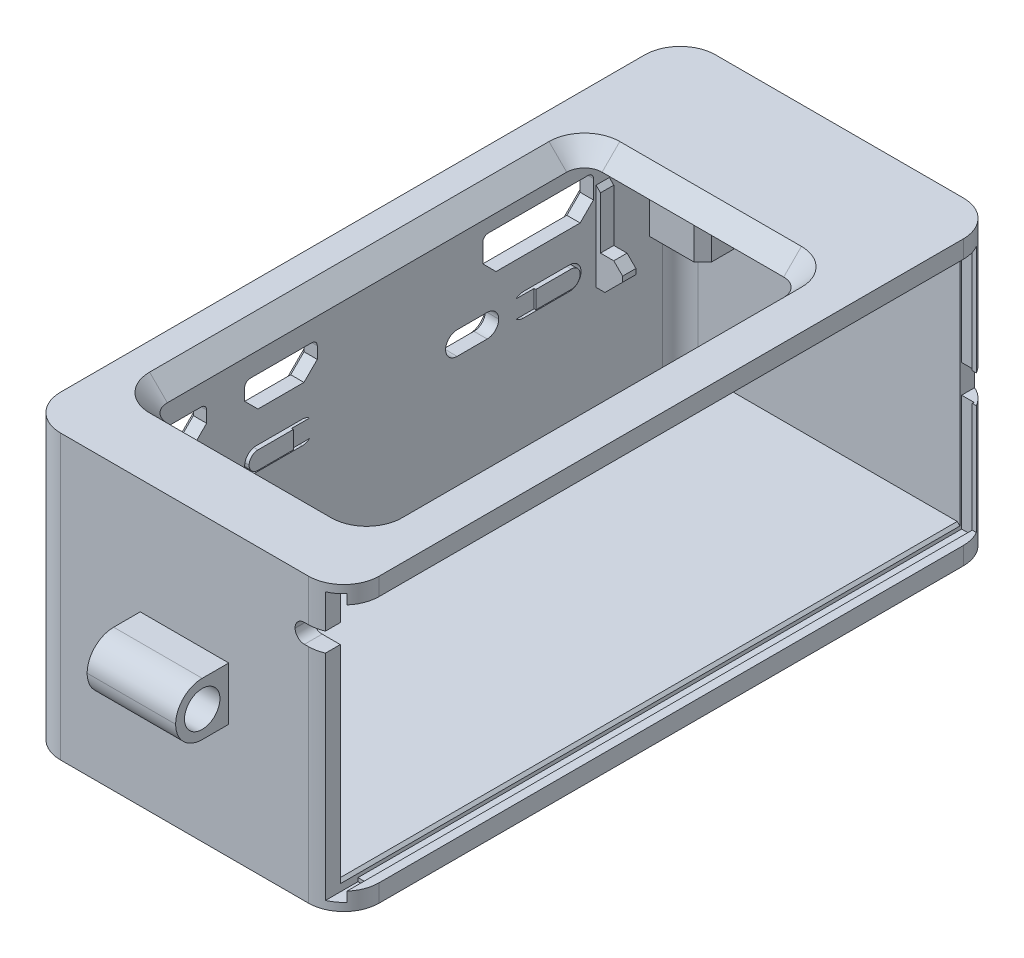
SolidWorks part; units mm, degrees
ref_plane "前视基准面" through (0, 0, 0) normal (0, 0, 1) x (1, 0, 0)
ref_plane "上视基准面" through (0, 0, 0) normal (0, 1, 0) x (1, 0, 0)
ref_plane "右视基准面" through (0, 0, 0) normal (1, 0, 0) x (0, 0, -1)
sketch "草图1" plane through (0, 0, 0) normal (1, 0, 0) x (0, 0, -1)
  line L1 (-54.0501, 29.0398) -> (19.9499, 29.0398)
  line L2 (-54.0501, 29.0398) -> (-54.0501, -2.9602)
  line L3 (-54.0501, -2.9602) -> (19.9499, -2.9602)
  line L4 (19.9499, 29.0398) -> (19.9499, -2.9602)
  dimension "D1" = 74
  dimension "D2" = 32
extrude "凸台-拉伸1" add sketch "草图1" along normal blind 36
sketch "草图2" plane through (36, 0, 0) normal (1, 0, 0) x (0, 0, -1)
  line L8 (17.9499, -0.9602) -> (17.9499, 27.0398)
  line L9 (-52.0501, -0.9602) -> (17.9499, -0.9602)
  line L10 (-52.0501, 27.0398) -> (-52.0501, -0.9602)
  line L11 (17.9499, 27.0398) -> (-52.0501, 27.0398)
  line L12 (17.9499, -0.9602) -> (17.9499, 27.0398)
  line L13 (-52.0501, -0.9602) -> (17.9499, -0.9602)
  line L14 (-52.0501, 27.0398) -> (-52.0501, -0.9602)
  line L15 (17.9499, 27.0398) -> (-52.0501, 27.0398)
  dimension "D1" = 2
extrude "切除-拉伸1" cut sketch "草图2" against normal blind 34
fillet "圆角1" radius 2 2 edges at (2, 13.0398, -17.9499) (2, 13.0398, 52.0501)
fillet "圆角2" radius 4 4 edges at (0, 13.0398, -19.9499) (0, 13.0398, 54.0501) (36, 13.0398, 54.0501) (36, 13.0398, -19.9499)
sketch "草图3" plane through (0, 29.0398, 0) normal (0, 1, 0) x (1, 0, 0)
  line L0 (32, 19.9499) -> (4, 19.9499) construction
  line L1 (29.59, 4.0599) -> (5.07, 4.0599)
  line L2 (29.59, 4.0599) -> (29.59, -45.0601)
  line L3 (29.59, -45.0601) -> (5.07, -45.0601)
  line L4 (5.07, 4.0599) -> (5.07, -45.0601)
  line L5 (36, 15.9499) -> (36, -50.0501) construction
  line L6 (32, -54.0501) -> (4, -54.0501) construction
  line L7 (0, 15.9499) -> (0, -50.0501) construction
  dimension "D1" = 15.89
  dimension "D2" = 6.41
  dimension "D3" = 8.99
  dimension "D4" = 5.07
extrude "切除-拉伸2" cut sketch "草图3" against normal blind 10
fillet "圆角3" radius 2 4 edges at (5.07, 28.0398, 45.0601) (29.59, 28.0398, 45.0601) (29.59, 28.0398, -4.0599) (5.07, 28.0398, -4.0599)
chamfer "倒角1" distance 2 angle 45 8 edges at (17.33, 29.0398, 45.0601) (29.0042, 29.0398, 44.4744) (5.6558, 29.0398, 44.4744) (29.59, 29.0398, 20.5001) (5.07, 29.0398, 20.5001) (29.0042, 29.0398, -3.4741) (5.6558, 29.0398, -3.4741) (17.33, 29.0398, -4.0599)
sketch "草图4" plane through (0, 0, 0) normal (-1, 0, 0) x (0, 0, 1)
  line L0 (-15.9499, 29.0398) -> (50.0501, 29.0398) construction
  line L1 (-8.1499, 22.4398) -> (4.3501, 22.4398)
  line L2 (-8.1499, 22.4398) -> (-8.1499, 18.2398)
  line L3 (-8.1499, 18.2398) -> (4.3501, 18.2398)
  line L4 (4.3501, 22.4398) -> (4.3501, 18.2398)
  line L5 (23.0501, 21.6812) -> (31.2501, 21.6812)
  line L6 (23.0501, 21.6812) -> (23.0501, 18.2398)
  line L7 (23.0501, 18.2398) -> (31.2501, 18.2398)
  line L8 (31.2501, 21.6812) -> (31.2501, 18.2398)
  line L9 (35.5501, 21.6398) -> (43.7501, 21.6398)
  line L10 (35.5501, 21.6398) -> (35.5501, 18.2398)
  line L11 (35.5501, 18.2398) -> (43.7501, 18.2398)
  line L12 (43.7501, 21.6398) -> (43.7501, 18.2398)
  line L13 (-6.7499, 14.7398) -> (1.0501, 14.7398)
  line L14 (-6.7499, 14.7398) -> (-6.7499, 12.1398)
  line L15 (-6.7499, 12.1398) -> (1.0501, 12.1398)
  line L16 (1.0501, 14.7398) -> (1.0501, 12.1398)
  line L17 (23.4501, 14.7398) -> (31.2501, 14.7398)
  line L18 (23.4501, 14.7398) -> (23.4501, 12.1398)
  line L19 (23.4501, 12.1398) -> (31.2501, 12.1398)
  line L20 (31.2501, 14.7398) -> (31.2501, 12.1398)
  line L21 (33.8696, 14.7398) -> (43.3696, 14.7398)
  line L22 (33.8696, 14.7398) -> (33.8696, 11.5398)
  line L23 (33.8696, 11.5398) -> (43.3696, 11.5398)
  line L24 (43.3696, 14.7398) -> (43.3696, 11.5398)
  line L25 (54.0501, 29.0398) -> (54.0501, -2.9602) construction
  line L27 (8.5501, 14.7398) -> (2.5501, 14.7398)
  line L28 (8.5501, 14.7398) -> (8.5501, 12.1398)
  line L29 (8.5501, 12.1398) -> (2.5501, 12.1398)
  line L30 (2.5501, 14.7398) -> (2.5501, 12.1398)
  dimension "D1" = 14.3
  dimension "D2" = 3.2
  dimension "D3" = 2.6
  dimension "D4" = 7.8
  dimension "D5" = 7.8
  dimension "D6" = 8.2
  dimension "D7" = 8.2
  dimension "D8" = 3.4
  dimension "D9" = 12.5
  dimension "D10" = 4.2
  dimension "D11" = 10.8
  dimension "D12" = 10.3
  dimension "D13" = 4.3
  dimension "D14" = 18.7
  dimension "D15" = 9.5
  dimension "D16" = 53
  dimension "D17" = 1.5
  dimension "D18" = 6
extrude "切除-拉伸3" cut sketch "草图4" against normal blind 10
fillet "圆角8" radius 1.3 4 edges at (1, 14.7398, 2.5501) (1, 14.7398, 8.5501) (1, 12.1398, 8.5501) (1, 12.1398, 2.5501)
sketch "草图5" plane through (2, 0, 0) normal (1, 0, 0) x (0, 0, -1)
  line L0 (-23.4501, 12.1398) -> (-23.4501, 14.7398) construction
  line L1 (-23.4501, 14.4398) -> (-30.9501, 14.4398)
  line L2 (-23.4501, 14.4398) -> (-23.4501, 12.4398)
  line L3 (-23.4501, 12.4398) -> (-30.9501, 12.4398)
  line L4 (-30.9501, 14.4398) -> (-30.9501, 12.4398)
  line L5 (-1.0501, 14.7398) -> (-1.0501, 12.1398) construction
  line L6 (-1.0501, 12.4398) -> (6.4499, 12.4398)
  line L7 (-1.0501, 12.4398) -> (-1.0501, 14.4398)
  line L8 (-1.0501, 14.4398) -> (6.4499, 14.4398)
  line L9 (6.4499, 12.4398) -> (6.4499, 14.4398)
  line L10 (-23.4501, 14.7398) -> (-31.2501, 14.7398) construction
  line L11 (-31.2501, 12.1398) -> (-23.4501, 12.1398) construction
  line L12 (-31.2501, 14.7398) -> (-31.2501, 12.1398) construction
  line L13 (6.7499, 14.7398) -> (-1.0501, 14.7398) construction
  line L14 (-1.0501, 12.1398) -> (6.7499, 12.1398) construction
  line L15 (6.7499, 12.1398) -> (6.7499, 14.7398) construction
  dimension "D1" = 0.3
  dimension "D2" = 0.3
  dimension "D3" = 0.3
  dimension "D4" = 0.3
  dimension "D5" = 0.3
  dimension "D6" = 0.3
extrude "凸台-拉伸2" add sketch "草图5" against normal blind 1.2
sketch "草图6" plane through (0.8, 0, 0) normal (-1, 0, 0) x (0, 0, 1)
  line L0 (1.0501, 12.4398) -> (-6.4499, 12.4398) construction
  line L1 (-6.4499, 14.4398) -> (-1.4499, 14.4398)
  line L2 (-6.4499, 14.4398) -> (-6.4499, 12.4398)
  line L3 (-6.4499, 12.4398) -> (-1.4499, 12.4398)
  line L4 (-1.4499, 14.4398) -> (-1.4499, 12.4398)
  line L5 (30.9501, 12.4398) -> (23.4501, 12.4398) construction
  line L6 (30.9501, 14.4398) -> (25.9501, 14.4398)
  line L7 (30.9501, 14.4398) -> (30.9501, 12.4398)
  line L8 (30.9501, 12.4398) -> (25.9501, 12.4398)
  line L9 (25.9501, 14.4398) -> (25.9501, 12.4398)
  dimension "D1" = 5
  dimension "D2" = 5
extrude "凸台-拉伸3" add sketch "草图6" along normal blind 1.5 and the other way blind 1.4
fillet "圆角4" radius 0.6 10 edges at (1, 11.5398, 33.8696) (1, 14.7398, 33.8696) (1, 14.7398, 43.3696) (1, 11.5398, 43.3696) (1, 21.6398, 35.5501) (1, 21.6398, 43.7501) (1, 21.6812, 31.2501) (1, 21.6812, 23.0501) (1, 22.4398, -8.1499) (1, 22.4398, 4.3501)
chamfer "倒角2" distance 1.5 angle 45 6 edges at (1, 18.2398, 43.7501) (1, 18.2398, 35.5501) (1, 18.2398, 31.2501) (1, 18.2398, 23.0501) (1, 18.2398, 4.3501) (1, 18.2398, -8.1499)
fillet "圆角5" radius 1 8 edges at (0.05, 12.4398, 25.9501) (0.05, 14.4398, 25.9501) (0.75, 12.4398, 30.9501) (0.75, 14.4398, 30.9501) (0.05, 12.4398, -1.4499) (0.05, 14.4398, -1.4499) (0.75, 12.4398, -6.4499) (0.75, 14.4398, -6.4499)
chamfer "倒角10" distance 0.2 angle 45 12 edges at (-0.7, 12.4398, 28.4501) (-0.7, 12.7327, 30.6572) (-0.7, 12.7327, 26.243) (-0.7, 14.1469, 30.6572) (-0.7, 14.1469, 26.243) (-0.7, 14.4398, 28.4501) (-0.7, 12.4398, -3.9499) (-0.7, 12.7327, -1.7428) (-0.7, 12.7327, -6.157) (-0.7, 14.1469, -1.7428) (-0.7, 14.1469, -6.157) (-0.7, 14.4398, -3.9499)
fillet "圆角6" radius 1.3 8 edges at (1, 14.7398, 1.0501) (1, 12.1398, 1.0501) (1, 12.1398, -6.7499) (1, 14.7398, -6.7499) (1, 14.7398, 23.4501) (1, 12.1398, 23.4501) (1, 12.1398, 31.2501) (1, 14.7398, 31.2501)
chamfer "倒角4" distance 0.5 angle 45 50 edges at (0, 12.1398, -2.8499) (0, 12.5206, 0.6694) (0, 12.5206, -6.3691) (0, 14.359, 0.6694) (0, 14.359, -6.3691) (0, 14.7398, -2.8499) (0, 18.9898, -7.3999) (0, 18.2398, -1.8999) (0, 18.9898, 3.6001) (0, 20.7898, 4.3501) (0, 20.7898, -8.1499) (0, 22.2641, 4.1744) (0, 22.2641, -7.9741) (0, 22.4398, -1.8999) (0, 11.5398, 38.6196) (0, 11.7155, 43.1938) (0, 11.7155, 34.0453) (0, 13.1398, 43.3696) (0, 13.1398, 33.8696) (0, 14.5641, 43.1938) (0, 14.5641, 34.0453) (0, 14.7398, 38.6196) (0, 12.1398, 27.3501) (0, 12.5206, 30.8694) (0, 12.5206, 23.8309) (0, 14.359, 30.8694) (0, 14.359, 23.8309) (0, 14.7398, 27.3501) (0, 20.4105, 23.0501) (0, 21.5055, 23.2259) (0, 21.6812, 27.1501) (0, 21.5055, 31.0744) (0, 18.9898, 23.8001) (0, 18.2398, 27.1501) (0, 18.9898, 30.5001) (0, 20.4105, 31.2501) (0, 18.9898, 43.0001) (0, 18.2398, 39.6501) (0, 18.9898, 36.3001) (0, 20.3898, 35.5501) (0, 21.4641, 35.7259) (0, 21.6398, 39.6501) (0, 20.3898, 43.7501) (0, 21.4641, 43.5744) (0, 12.5206, 8.1694) (0, 12.1398, 5.5501) (0, 12.5206, 2.9309) (0, 14.359, 8.1694) (0, 14.7398, 5.5501) (0, 14.359, 2.9309)
sketch "草图7" plane through (2, 0, 0) normal (1, 0, 0) x (0, 0, -1)
  line L0 (15.9499, 27.0398) -> (-50.0501, 27.0398) construction
  line L1 (-46.0501, 21.0398) -> (-44.5501, 21.0398)
  line L2 (-46.0501, 21.0398) -> (-46.0501, 11.0398)
  line L3 (-46.0501, 11.0398) -> (-44.5501, 11.0398)
  line L4 (-44.5501, 21.0398) -> (-44.5501, 11.0398)
  line L5 (8.4499, 21.0398) -> (9.9499, 21.0398)
  line L6 (8.4499, 21.0398) -> (8.4499, 11.0398)
  line L7 (8.4499, 11.0398) -> (9.9499, 11.0398)
  line L8 (9.9499, 21.0398) -> (9.9499, 11.0398)
  line L11 (17.9499, -0.9602) -> (17.9499, 27.0398) construction
  line L12 (-52.0501, 27.0398) -> (-52.0501, -0.9602) construction
  dimension "D1" = 6
  dimension "D2" = 10
  dimension "D3" = 1.5
  dimension "D4" = 1.5
  dimension "D5" = 8
  dimension "D6" = 6
extrude "凸台-拉伸4" add sketch "草图7" along normal blind 0.5
sketch "草图10" plane through (2.5, 0, 0) normal (1, 0, 0) x (0, 0, -1)
  line L1 (-46.0501, 11.0398) -> (-44.5501, 11.0398)
  line L2 (-46.0501, 11.0398) -> (-46.0501, 14.6398)
  line L3 (-46.0501, 14.6398) -> (-44.5501, 14.6398)
  line L4 (-44.5501, 11.0398) -> (-44.5501, 14.6398)
  line L7 (8.4499, 11.0398) -> (9.9499, 11.0398)
  line L8 (8.4499, 11.0398) -> (8.4499, 14.6398)
  line L9 (8.4499, 14.6398) -> (9.9499, 14.6398)
  line L10 (9.9499, 11.0398) -> (9.9499, 14.6398)
  dimension "D1" = 3.6
extrude "凸台-拉伸6" add sketch "草图10" along normal blind 2.5
chamfer "倒角7" distance 1 angle 45 2 edges at (5, 14.6398, -9.1999) (5, 14.6398, 45.3001)
chamfer "倒角8" distance 2 angle 45 2 edges at (5, 11.0398, 45.3001) (5, 11.0398, -9.1999)
chamfer "倒角5" distance 0.5 angle 45 2 edges at (2.5, 21.0398, 45.3001) (2.5, 21.0398, -9.1999)
sketch "草图8" plane through (2, 0, 0) normal (1, 0, 0) x (0, 0, -1)
  line L1 (-52.0501, 22.2398) -> (-48.0501, 22.2398)
  line L2 (-52.0501, 22.2398) -> (-52.0501, 24.2398)
  line L3 (-52.0501, 24.2398) -> (-48.0501, 24.2398)
  line L4 (-48.0501, 22.2398) -> (-48.0501, 24.2398)
  line L6 (17.9499, 24.2398) -> (11.9499, 24.2398)
  line L7 (17.9499, 24.2398) -> (17.9499, 22.2398)
  line L8 (17.9499, 22.2398) -> (11.9499, 22.2398)
  line L9 (11.9499, 24.2398) -> (11.9499, 22.2398)
  line L10 (15.9499, 27.0398) -> (-50.0501, 27.0398) construction
  line L11 (17.9499, -0.9602) -> (17.9499, 27.0398) construction
  line L12 (-52.0501, 27.0398) -> (-52.0501, -0.9602) construction
  dimension "D1" = 2.8
  dimension "D2" = 2
  dimension "D3" = 4
  dimension "D4" = 6
extrude "凸台-拉伸5" add sketch "草图8" along normal blind 5
chamfer "倒角6" distance 1 angle 45 2 edges at (7, 24.2398, -14.9499) (7, 24.2398, 50.0501)
sketch "草图12" plane through (0, 0, 54.0501) normal (0, 0, 1) x (1, 0, 0)
  line L0 (4, -0.9602) -> (35.4641, -0.9602) construction
  line L1 (36, 27.0398) -> (33.6, 27.0398)
  line L2 (36, 27.0398) -> (36, -0.9602)
  line L3 (36, -0.9602) -> (33.6, -0.9602)
  line L4 (33.6, 27.0398) -> (33.6, -0.9602)
  dimension "D1" = 2.4
extrude "切除-拉伸5" cut sketch "草图12" against normal blind 10.8
sketch "草图11" plane through (0, -0.9602, 0) normal (0, 1, 0) x (1, 0, 0)
  line L0 (32, 19.9499) -> (4, 19.9499) construction
  line L1 (35, 17.9499) -> (33.6, 17.9499)
  line L2 (35, 17.9499) -> (35, -54.0501)
  line L3 (35, -54.0501) -> (33.6, -54.0501)
  line L4 (33.6, 17.9499) -> (33.6, -54.0501)
  line L5 (32, -54.0501) -> (4, -54.0501) construction
  line L6 (36, -50.0501) -> (36, 15.9499) construction
  dimension "D1" = 2
  dimension "D2" = 0
  dimension "D3" = 1
  dimension "D4" = 1.4
extrude "切除-拉伸4" cut sketch "草图11" against normal blind 0.7
sketch "草图13" plane through (0, 27.0398, 0) normal (0, -1, 0) x (1, 0, 0)
  line L10 (33.6, -17.9499) -> (35, -17.9499)
  line L11 (33.6, 54.0501) -> (33.6, -17.9499)
  line L12 (35, 54.0501) -> (33.6, 54.0501)
  line L13 (35, -17.9499) -> (35, 54.0501)
  line L14 (33.6, -17.9499) -> (35, -17.9499)
  line L15 (33.6, 54.0501) -> (33.6, -17.9499)
  line L16 (35, 54.0501) -> (33.6, 54.0501)
  line L17 (35, -17.9499) -> (35, 54.0501)
  dimension "D1" = 0
extrude "切除-拉伸6" cut sketch "草图13" against normal blind 0.7
sketch "草图14" plane through (0, -1.6602, 0) normal (0, 1, 0) x (1, 0, 0)
  line L1 (33.6, -54.0501) -> (35, -54.0501)
  line L2 (33.6, -54.0501) -> (33.6, -50.0501)
  line L3 (33.6, -50.0501) -> (35, -50.0501)
  line L4 (35, -54.0501) -> (35, -50.0501)
  line L5 (32, -54.0501) -> (4, -54.0501) construction
  line L6 (33.6, -53.7162) -> (33.6, 17.9499) construction
  dimension "D1" = 4
extrude "切除-拉伸7" cut sketch "草图14" against normal blind 0.4
sketch "草图15" plane through (0, 27.7398, 0) normal (0, -1, 0) x (1, 0, 0)
  line L3 (35, 50.0501) -> (35, 52.6959)
  line L4 (33.6, 50.0501) -> (35, 50.0501)
  line L5 (33.6, 53.7162) -> (33.6, 50.0501)
  line L7 (33.6, 50.0501) -> (35, 50.0501)
  line L8 (33.6, 53.7162) -> (33.6, 50.0501)
  line L10 (35, 50.0501) -> (35, 52.6959)
  arc A1 (35, 52.6959) -> (33.6, 53.7162) centre (32, 50.0501) ccw
  arc A2 (35, 52.6959) -> (33.6, 53.7162) centre (32, 50.0501) ccw
  dimension "D1" = 0
extrude "切除-拉伸8" cut sketch "草图15" against normal blind 0.4
sketch "草图16" plane through (0, 0, -17.9499) normal (0, 0, 1) x (1, 0, 0)
  line L0 (33.6, 28.1398) -> (33.6, -2.0602) construction
  line L1 (33.6, 27.7398) -> (35, 27.7398)
  line L2 (33.6, 27.7398) -> (33.6, -1.6602)
  line L3 (33.6, -1.6602) -> (35, -1.6602)
  line L4 (35, 27.7398) -> (35, -1.6602)
extrude "切除-拉伸9" cut sketch "草图16" against normal blind 0.2
chamfer "倒角9" distance 0.3 angle 45 2 edges at (33.6, 27.0398, 17.0501) (33.6, -0.9602, 17.0501)
ref_plane "基准面4" through (0, 13.0398, 0) normal (0, -1, 0) x (-1, 0, 0)
sketch "草图19" plane through (0, 0, -18.1499) normal (0, 0, 1) x (1, 0, 0)
  line L0 (35, 13.0398) -> (40.512, 13.0398) construction
  line L1 (35.4641, -0.9602) -> (35.4641, 27.0398) construction
  line L3 (34.3, 27.7398) -> (34.3, 24.7272) construction
  line L4 (33.6, 27.7398) -> (35, 27.7398) construction
  line L6 (33.6, 14.6398) -> (35.4641, 14.6398)
  line L7 (33.6, 14.6398) -> (33.6, 11.4398)
  line L8 (33.6, 11.4398) -> (35.4641, 11.4398)
  line L9 (35.4641, 14.6398) -> (35.4641, 11.4398)
  line L10 (33.6, 14.6398) -> (35.4641, 11.4398) construction
  line L11 (33.6, 11.4398) -> (35.4641, 14.6398) construction
  point P2 (34.3, 13.0398)
  point P10 (34.5321, 13.0398)
  point P13 (35.4641, 13.0398)
  point P16 (34.3, 27.7398)
  dimension "D1" = 3.2
extrude "切除-拉伸11" cut sketch "草图19" against normal blind 10 and the other way blind 2
sketch "草图20" plane through (0, 0, 54.0501) normal (0, 0, 1) x (1, 0, 0)
  line L0 (33.6, 24.2398) -> (33.6, 28.1198) construction
  line L1 (33.6, 24.2898) -> (30.5, 24.2898)
  line L2 (33.6, 24.2898) -> (33.6, 22.1398)
  line L3 (33.6, 22.1398) -> (30.5, 22.1398)
  line L4 (30.5, 24.2898) -> (30.5, 22.1398)
  line L5 (32, 29.0398) -> (4, 29.0398) construction
  dimension "D1" = 4.75
  dimension "D2" = 2.15
  dimension "D3" = 3.1
extrude "切除-拉伸12" cut sketch "草图20" against normal up to next
fillet "圆角9" radius 1.05 2 edges at (30.5, 24.2898, 53.0501) (30.5, 22.1398, 53.0501)
sketch "草图21" plane through (0, 0, -19.9499) normal (0, 0, -1) x (-1, 0, 0)
  line L0 (-25, 19.5398) -> (-14, 19.5398) construction
  line L1 (-25, 21.0398) -> (-14, 21.0398)
  line L2 (-25, 18.0398) -> (-14, 18.0398)
  line L3 (-4, -2.9602) -> (-4, 29.0398) construction
  line L4 (-32, 29.0398) -> (-4, 29.0398) construction
  arc A0 (-25, 21.0398) -> (-25, 18.0398) centre (-25, 19.5398) ccw
  arc A1 (-14, 18.0398) -> (-14, 21.0398) centre (-14, 19.5398) ccw
  point P2 (-19.5, 19.5398)
  dimension "D4" = 1.5
  dimension "D1" = 10
  dimension "D2" = 9.5
  dimension "D3" = 11
extrude "切除-拉伸13" cut sketch "草图21" against normal up to next
sketch "草图22" plane through (0, -2.9602, 0) normal (0, -1, 0) x (1, 0, 0)
  line L0 (7.07, -6.0599) -> (27.59, -6.0599) construction
  line B0 (12.438, 7.4573) -> (11.965, 6.6368)
  line B1 (11.965, 6.6368) -> (9.5089, 2.3799)
  line B2 (9.5089, 2.3799) -> (9.0302, 1.5593)
  line B3 (9.0302, -0.1617) -> (9.5089, -0.9823)
  line B4 (9.5089, -0.9823) -> (11.965, -5.2392)
  line B5 (11.965, -5.2392) -> (12.438, -6.0599)
  line B6 (13.9253, -6.9204) -> (20.7409, -6.9204)
  line B7 (22.2283, -6.0599) -> (22.7013, -5.2392)
  line B8 (22.7013, -5.2392) -> (25.1574, -0.9823)
  line B9 (25.1574, -0.9823) -> (25.6361, -0.1617)
  line B10 (25.6361, 1.5593) -> (25.1574, 2.3799)
  line B11 (25.1574, 2.3799) -> (22.7013, 6.6368)
  line B12 (22.7013, 6.6368) -> (22.2283, 7.4573)
  line B13 (20.7409, 8.3178) -> (13.9253, 8.3178)
  line B14 (13.1161, -4.9657) -> (10.073, 0.2999)
  line B15 (10.073, 1.1034) -> (13.1218, 6.3404)
  line B16 (13.8228, 6.3461) -> (16.8658, 1.2573)
  line B17 (22.0231, 2.8358) -> (22.3536, 2.2431)
  line B18 (22.4505, 2.1861) -> (24.1601, 2.1861)
  line B19 (24.257, 2.1292) -> (24.8838, 1.0236)
  line B20 (24.787, 0.8583) -> (19.51, 0.8583)
  line B21 (19.4131, 0.9153) -> (18.3475, 2.7959)
  line B22 (21.6698, 6.7393) -> (22.291, 5.6452)
  line B23 (22.1941, 5.4799) -> (19.681, 5.4799)
  line B24 (19.5841, 5.537) -> (18.9686, 6.6311)
  line B25 (19.0655, 6.7963) -> (21.5729, 6.7963)
  line B26 (21.0088, 2.7674) -> (21.2709, 2.2431)
  line B27 (21.1512, 2.1861) -> (19.8064, 2.1861)
  line B28 (19.7095, 2.2431) -> (19.4359, 2.7332)
  line B29 (14.404, 12.3126) -> (14.404, 10.4377)
  line B30 (14.404, 10.4377) -> (20.9689, 10.4377)
  line B31 (20.9689, 10.4377) -> (20.9689, 11.2698)
  line B32 (20.9689, 11.2698) -> (18.3646, 11.2698)
  line B33 (18.3646, 11.2698) -> (18.3646, 12.3582)
  line B34 (17.6921, 12.25) -> (17.6921, 11.2698)
  line B35 (17.6921, 11.2698) -> (15.0765, 11.2698)
  line B36 (15.0765, 11.2698) -> (15.0765, 12.2158)
  line B37 (16.1022, 15.8514) -> (20.9689, 15.8514)
  line B38 (20.9689, 15.8514) -> (20.9689, 16.6665)
  line B39 (20.9689, 16.6665) -> (16.1022, 16.6665)
  line B40 (16.1022, 16.6665) -> (16.1022, 15.8514)
  line B41 (17.1793, 21.3735) -> (16.8487, 20.5415)
  line B42 (16.0623, 21.6983) -> (15.0594, 22.4962)
  line B43 (18.0227, 19.265) -> (18.3817, 20.1141)
  line B44 (19.0313, 18.564) -> (20.1369, 17.658)
  line B45 (15.8743, 26.4795) -> (19.2137, 26.4795)
  line B46 (18.8262, 25.0377) -> (15.8743, 25.0377)
  line B47 (15.8743, 25.0377) -> (15.8743, 23.4478)
  line B48 (15.8743, 23.4478) -> (19.0256, 23.4478)
  line B49 (20.2679, 26.6277) -> (20.2679, 26.6618)
  line B50 (20.2679, 26.6618) -> (20.9689, 26.7759)
  line B51 (20.9689, 26.7759) -> (20.9689, 28.0751)
  line B52 (20.9689, 28.0751) -> (15.8743, 28.0751)
  line B53 (15.8743, 28.0751) -> (15.8743, 26.4795)
  line B54 (19.9659, 31.9274) -> (19.9659, 31.1239)
  line B55 (17.0254, 33.0216) -> (17.0254, 33.8079)
  line B56 (17.0254, 33.8079) -> (15.8743, 33.8079)
  line B57 (15.8743, 33.8079) -> (15.8743, 31.9388)
  line B58 (18.9174, 29.6878) -> (18.9516, 29.6878)
  line B59 (20.7808, 29.591) -> (20.8264, 29.591)
  line B60 (21.1854, 31.141) -> (21.1854, 31.6254)
  line B61 (16.4156, 34.2638) -> (17.4642, 34.8223)
  line B62 (20.456, 37.0676) -> (20.456, 37.1075)
  line B63 (20.456, 37.1075) -> (20.9689, 37.2214)
  line B64 (20.9689, 37.2214) -> (20.9689, 38.5207)
  line B65 (20.9689, 38.5207) -> (18.074, 38.5207)
  line B66 (18.6381, 36.9251) -> (19.453, 36.9251)
  line B67 (16.7576, 41.0111) -> (16.7576, 40.9769)
  line B68 (16.7576, 40.9769) -> (15.8743, 40.8686)
  line B69 (15.8743, 40.8686) -> (15.8743, 39.5693)
  line B70 (15.8743, 39.5693) -> (20.9689, 39.5693)
  line B71 (20.9689, 39.5693) -> (20.9689, 41.1536)
  line B72 (20.9689, 41.1536) -> (18.0569, 41.1536)
  line B73 (17.2248, 42.8118) -> (15.8515, 43.0796)
  line B74 (21.2709, 2.2431) -> (22.3536, 2.2431)
  line B75 (21.1512, 2.1861) -> (22.4505, 2.1861)
  spline B76 degree 3 poles (9.0302, 1.5593) (8.882, 1.2914) (8.8022, 0.9951) (8.8022, 0.6988) knots 3 3 3 3 4 4 4 4
  spline B77 degree 3 poles (8.8022, 0.6988) (8.8022, 0.4025) (8.882, 0.1061) (9.0302, -0.1617) knots 4 4 4 4 5 5 5 5
  spline B78 degree 3 poles (12.438, -6.0599) (12.7457, -6.5898) (13.3156, -6.9204) (13.9253, -6.9204) knots 8 8 8 8 9 9 9 9
  spline B79 degree 3 poles (20.7409, -6.9204) (21.3564, -6.9204) (21.9206, -6.5898) (22.2283, -6.0599) knots 10 10 10 10 11 11 11 11
  spline B80 degree 3 poles (25.6361, -0.1617) (25.7899, 0.1061) (25.864, 0.4025) (25.864, 0.6988) knots 14 14 14 14 15 15 15 15
  spline B81 degree 3 poles (25.864, 0.6988) (25.864, 0.9951) (25.7899, 1.2914) (25.6361, 1.5593) knots 15 15 15 15 16 16 16 16
  spline B82 degree 3 poles (22.2283, 7.4573) (21.9206, 7.993) (21.3564, 8.3178) (20.7409, 8.3178) knots 19 19 19 19 20 20 20 20
  spline B83 degree 3 poles (13.9253, 8.3178) (13.3156, 8.3178) (12.7457, 7.993) (12.438, 7.4573) knots 21 21 21 21 22 22 22 22
  spline B84 degree 2 poles (16.8658, 0.146) (13.8911, -5.0056) (13.8854, -5.017) knots 0 0 0 1 1 1
  spline B85 degree 3 poles (13.8854, -5.017) (13.6917, -5.2848) (13.2814, -5.2563) (13.1161, -4.9657) knots 1 1 1 1 2 2 2 2
  spline B86 degree 3 poles (10.073, 0.2999) (9.9306, 0.5449) (9.9306, 0.8527) (10.073, 1.1034) knots 3 3 3 3 4 4 4 4
  spline B87 degree 3 poles (13.1218, 6.3404) (13.2757, 6.6082) (13.6632, 6.6139) (13.8228, 6.3461) knots 5 5 5 5 6 6 6 6
  spline B88 degree 3 poles (16.8658, 1.2573) (17.0653, 0.9153) (17.0653, 0.4879) (16.8658, 0.146) knots 7 7 7 7 8 8 8 8
  spline B89 degree 3 poles (24.1601, 2.1861) (24.2, 2.1861) (24.2342, 2.169) (24.257, 2.1292) knots 3 3 3 3 4 4 4 4
  spline B90 degree 3 poles (24.8838, 1.0236) (24.9237, 0.9495) (24.8725, 0.8583) (24.787, 0.8583) knots 5 5 5 5 6 6 6 6
  spline B91 degree 3 poles (19.51, 0.8583) (19.4701, 0.8583) (19.4302, 0.8754) (19.4131, 0.9153) knots 7 7 7 7 8 8 8 8
  spline B92 degree 3 poles (18.3475, 2.7959) (17.6579, 4.0154) (17.5212, 5.024) (18.8889, 5.024) knots 9 9 9 9 10 10 10 10
  spline B93 degree 3 poles (18.8889, 5.024) (20.2053, 5.024) (21.3621, 4.004) (22.0231, 2.8358) knots 10 10 10 10 11 11 11 11
  spline B94 degree 3 poles (21.5729, 6.7963) (21.6128, 6.7963) (21.6527, 6.7735) (21.6698, 6.7393) knots 0 0 0 0 1 1 1 1
  spline B95 degree 3 poles (22.291, 5.6452) (22.3309, 5.5711) (22.2795, 5.4799) (22.1941, 5.4799) knots 2 2 2 2 3 3 3 3
  spline B96 degree 3 poles (19.681, 5.4799) (19.6411, 5.4799) (19.6069, 5.5027) (19.5841, 5.537) knots 4 4 4 4 5 5 5 5
  spline B97 degree 3 poles (18.9686, 6.6311) (18.9288, 6.7051) (18.98, 6.7963) (19.0655, 6.7963) knots 6 6 6 6 7 7 7 7
  spline B98 degree 3 poles (17.2989, 6.141) (17.0482, 6.5798) (17.1565, 6.8932) (17.5554, 6.8932) (17.9486, 6.8932) (18.4102, 6.5798) (18.6552, 6.141) knots 2 2 2 2 3 3 3 4 4 4 4
  spline B99 degree 3 poles (18.6552, 6.141) (18.9117, 5.6965) (18.8034, 5.3831) (18.4102, 5.3831) (18.0056, 5.3831) (17.5497, 5.6965) (17.2989, 6.141) knots 0 0 0 0 1 1 1 2 2 2 2
  spline B100 degree 3 poles (19.624, 3.7248) (20.1654, 3.7248) (20.644, 3.4171) (21.0088, 2.7674) knots 0 0 0 0 1 1 1 1
  spline B101 degree 3 poles (19.8064, 2.1861) (19.7665, 2.1861) (19.7266, 2.2089) (19.7095, 2.2431) knots 4 4 4 4 5 5 5 5
  spline B102 degree 3 poles (19.4359, 2.7332) (19.0712, 3.3714) (19.0655, 3.7248) (19.624, 3.7248) knots 6 6 6 6 7 7 7 7
  spline B103 degree 3 poles (18.3646, 12.3582) (18.3646, 13.7886) (17.715, 14.7745) (16.3302, 14.7745) knots 5 5 5 5 6 6 6 6
  spline B104 degree 3 poles (16.3302, 14.7745) (14.8941, 14.7745) (14.404, 13.7886) (14.404, 12.3126) knots 6 6 6 6 7 7 7 7
  spline B105 degree 3 poles (15.0765, 12.2158) (15.0765, 13.3669) (15.3785, 13.9482) (16.3302, 13.9482) knots 3 3 3 3 4 4 4 4
  spline B106 degree 3 poles (16.3302, 13.9482) (17.2704, 13.9482) (17.6921, 13.4068) (17.6921, 12.25) knots 4 4 4 4 5 5 5 5
  spline B107 degree 3 poles (15.0993, 16.2618) (15.0993, 16.5866) (14.877, 16.826) (14.575, 16.826) (14.2388, 16.826) (14.045, 16.5866) (14.045, 16.2618) knots 2 2 2 2 3 3 3 4 4 4 4
  spline B108 degree 3 poles (14.045, 16.2618) (14.045, 15.937) (14.2388, 15.6976) (14.575, 15.6976) (14.877, 15.6976) (15.0993, 15.937) (15.0993, 16.2618) knots 0 0 0 0 1 1 1 2 2 2 2
  spline B109 degree 3 poles (16.8487, 20.5415) (16.6151, 19.9545) (16.4726, 19.5328) (16.1022, 19.5328) knots 1 1 1 1 2 2 2 2
  spline B110 degree 3 poles (16.1022, 19.5328) (15.7489, 19.5328) (15.5494, 19.8349) (15.5494, 20.3306) knots 2 2 2 2 3 3 3 3
  spline B111 degree 3 poles (15.5494, 20.3306) (15.5494, 20.8492) (15.7261, 21.2595) (16.0623, 21.6983) knots 3 3 3 3 4 4 4 4
  spline B112 degree 3 poles (15.0594, 22.4962) (14.4724, 21.9149) (14.1761, 21.1) (14.1761, 20.3306) knots 5 5 5 5 6 6 6 6
  spline B113 degree 3 poles (14.1761, 20.3306) (14.1761, 18.9117) (15.0765, 17.9087) (16.1934, 17.9087) knots 6 6 6 6 7 7 7 7
  spline B114 degree 3 poles (16.1934, 17.9087) (17.1622, 17.9087) (17.7434, 18.564) (18.0227, 19.265) knots 7 7 7 7 8 8 8 8
  spline B115 degree 3 poles (18.3817, 20.1141) (18.621, 20.684) (18.7464, 21.0544) (19.1339, 21.0544) knots 9 9 9 9 10 10 10 10
  spline B116 degree 3 poles (19.1339, 21.0544) (19.4929, 21.0544) (19.7152, 20.7752) (19.7152, 20.1825) knots 10 10 10 10 11 11 11 11
  spline B117 degree 3 poles (19.7152, 20.1825) (19.7152, 19.6582) (19.4359, 19.037) (19.0313, 18.564) knots 11 11 11 11 12 12 12 12
  spline B118 degree 3 poles (20.1369, 17.658) (20.7694, 18.3475) (21.0943, 19.282) (21.0943, 20.1483) knots 13 13 13 13 14 14 14 14
  spline B119 degree 3 poles (21.0943, 20.1483) (21.0943, 21.761) (20.1198, 22.6955) (19.0085, 22.6955) knots 14 14 14 14 15 15 15 15
  spline B120 degree 3 poles (19.0085, 22.6955) (18.0683, 22.6955) (17.5098, 22.1998) (17.1793, 21.3735) knots 15 15 15 15 16 16 16 16
  spline B121 degree 3 poles (19.2137, 26.4795) (19.5898, 26.2117) (19.7323, 25.9894) (19.7323, 25.6304) knots 1 1 1 1 2 2 2 2
  spline B122 degree 3 poles (19.7323, 25.6304) (19.7323, 25.2258) (19.5328, 25.0377) (18.8262, 25.0377) knots 2 2 2 2 3 3 3 3
  spline B123 degree 3 poles (19.0256, 23.4478) (20.2964, 23.4478) (21.0943, 23.9208) (21.0943, 25.032) knots 6 6 6 6 7 7 7 7
  spline B124 degree 3 poles (21.0943, 25.032) (21.0943, 25.7273) (20.7694, 26.206) (20.2679, 26.6277) knots 7 7 7 7 8 8 8 8
  spline B125 degree 3 poles (19.9659, 31.1239) (19.9659, 30.5768) (19.8576, 30.3717) (19.624, 30.3717) knots 1 1 1 1 2 2 2 2
  spline B126 degree 3 poles (19.624, 30.3717) (19.453, 30.3717) (19.3732, 30.4115) (19.265, 30.5312) knots 2 2 2 2 3 3 3 3
  spline B127 degree 3 poles (19.265, 30.5312) (19.3276, 30.7535) (19.3562, 30.9586) (19.3562, 31.1296) knots 3 3 3 3 4 4 4 4
  spline B128 degree 3 poles (19.3562, 31.1296) (19.3562, 32.2579) (18.8376, 33.164) (17.6466, 33.164) knots 4 4 4 4 5 5 5 5
  spline B129 degree 3 poles (17.6466, 33.164) (17.4015, 33.164) (17.1679, 33.1013) (17.0254, 33.0216) knots 5 5 5 5 6 6 6 6
  spline B130 degree 3 poles (15.8743, 31.9388) (15.7888, 31.7051) (15.7489, 31.4259) (15.7489, 31.1296) knots 9 9 9 9 10 10 10 10
  spline B131 degree 3 poles (15.7489, 31.1296) (15.7489, 30.0298) (16.353, 28.9983) (17.601, 28.9983) knots 10 10 10 10 11 11 11 11
  spline B132 degree 3 poles (17.601, 28.9983) (18.1936, 28.9983) (18.6666, 29.3288) (18.9174, 29.6878) knots 11 11 11 11 12 12 12 12
  spline B133 degree 3 poles (18.9516, 29.6878) (19.1852, 29.3573) (19.5442, 29.1236) (19.9032, 29.1236) knots 13 13 13 13 14 14 14 14
  spline B134 degree 3 poles (19.9032, 29.1236) (20.3306, 29.1236) (20.5985, 29.3231) (20.7808, 29.591) knots 14 14 14 14 15 15 15 15
  spline B135 degree 3 poles (20.8264, 29.591) (21.0658, 29.1179) (21.4077, 28.8672) (21.8294, 28.8672) knots 16 16 16 16 17 17 17 17
  spline B136 degree 3 poles (21.8294, 28.8672) (22.7411, 28.8672) (23.1116, 29.8303) (23.1116, 31.0042) knots 17 17 17 17 18 18 18 18
  spline B137 degree 3 poles (23.1116, 31.0042) (23.1116, 32.7765) (22.348, 33.8878) (21.2709, 33.8878) knots 18 18 18 18 19 19 19 19
  spline B138 degree 3 poles (21.2709, 33.8878) (20.3477, 33.8878) (19.9659, 33.1811) (19.9659, 31.9274) knots 19 19 19 19 20 20 20 20
  spline B139 degree 3 poles (18.3988, 31.1296) (18.3988, 30.7649) (18.1309, 30.4857) (17.601, 30.4857) (17.0824, 30.4857) (16.8146, 30.7649) (16.8146, 31.1296) knots 2 2 2 2 3 3 3 4 4 4 4
  spline B140 degree 3 poles (16.8146, 31.1296) (16.8146, 31.5057) (17.0824, 31.7735) (17.601, 31.7735) (18.1309, 31.7735) (18.3988, 31.5057) (18.3988, 31.1296) knots 0 0 0 0 1 1 1 2 2 2 2
  spline B141 degree 3 poles (22.1143, 31.2549) (22.1143, 30.5996) (21.9376, 30.1722) (21.5786, 30.1722) knots 0 0 0 0 1 1 1 1
  spline B142 degree 3 poles (21.5786, 30.1722) (21.4077, 30.1722) (21.2652, 30.252) (21.1227, 30.4115) knots 1 1 1 1 2 2 2 2
  spline B143 degree 3 poles (21.1227, 30.4115) (21.1683, 30.5768) (21.1854, 30.7706) (21.1854, 31.141) knots 2 2 2 2 3 3 3 3
  spline B144 degree 3 poles (21.1854, 31.6254) (21.1854, 32.0983) (21.2481, 32.3662) (21.5501, 32.3662) knots 4 4 4 4 5 5 5 5
  spline B145 degree 3 poles (21.5501, 32.3662) (21.875, 32.3662) (22.1143, 31.9104) (22.1143, 31.2549) knots 5 5 5 5 6 6 6 6
  spline B146 degree 3 poles (15.7489, 36.4579) (15.7489, 35.6657) (16.0167, 34.9363) (16.4156, 34.2638) knots 0 0 0 0 1 1 1 1
  spline B147 degree 3 poles (17.4642, 34.8223) (17.1793, 35.3296) (17.0197, 35.7512) (17.0197, 36.1558) knots 2 2 2 2 3 3 3 3
  spline B148 degree 3 poles (17.0197, 36.1558) (17.0197, 36.6744) (17.259, 36.891) (17.6694, 36.9251) knots 3 3 3 3 4 4 4 4
  spline B149 degree 3 poles (17.6694, 36.9251) (17.8859, 34.9363) (18.4671, 34.0928) (19.5442, 34.0928) knots 4 4 4 4 5 5 5 5
  spline B150 degree 3 poles (19.5442, 34.0928) (20.3933, 34.0928) (21.0943, 34.6684) (21.0943, 35.6088) knots 5 5 5 5 6 6 6 6
  spline B151 degree 3 poles (21.0943, 35.6088) (21.0943, 36.1729) (20.8321, 36.6459) (20.456, 37.0676) knots 6 6 6 6 7 7 7 7
  spline B152 degree 3 poles (18.074, 38.5207) (16.4783, 38.5207) (15.7489, 37.7742) (15.7489, 36.4579) knots 11 11 11 11 12 12 12 12
  spline B153 degree 3 poles (19.453, 36.9251) (19.7038, 36.6915) (19.8576, 36.4806) (19.8576, 36.1558) knots 0 0 0 0 1 1 1 1
  spline B154 degree 3 poles (19.8576, 36.1558) (19.8576, 35.8253) (19.7152, 35.6088) (19.4188, 35.6088) knots 1 1 1 1 2 2 2 2
  spline B155 degree 3 poles (19.4188, 35.6088) (19.0598, 35.6088) (18.7749, 35.9336) (18.6381, 36.9251) knots 2 2 2 2 3 3 3 3
  spline B156 degree 3 poles (15.7489, 42.4642) (15.7489, 41.9513) (16.0794, 41.3872) (16.7576, 41.0111) knots 0 0 0 0 1 1 1 1
  spline B157 degree 3 poles (18.0569, 41.1536) (17.3844, 41.4214) (17.1451, 41.8773) (17.1451, 42.2534) knots 7 7 7 7 8 8 8 8
  spline B158 degree 3 poles (17.1451, 42.2534) (17.1451, 42.4813) (17.1793, 42.6295) (17.2248, 42.8118) knots 8 8 8 8 9 9 9 9
  spline B159 degree 3 poles (15.8515, 43.0796) (15.7888, 42.9372) (15.7489, 42.7663) (15.7489, 42.4642) knots 10 10 10 10 11 11 11 11
sketch_block_instance "块1-1"
sketch_block "块1"
extrude "切除-拉伸14" cut sketch "草图22" against normal blind 0.3
ref_plane "基准面5" through (13, 0, 0) normal (1, 0, 0) x (0, 0, -1)
sketch "草图23" plane through (13, 0, 0) normal (1, 0, 0) x (0, 0, -1)
  line L0 (-54.0501, -2.9602) -> (-54.0501, 22.1398) construction
  line L1 (-54.0501, 16.0398) -> (-60.0501, 16.0398)
  line L2 (-54.0501, 16.0398) -> (-54.0501, 10.0398)
  line L3 (-54.0501, 10.0398) -> (-60.0501, 10.0398)
  line L4 (-60.0501, 16.0398) -> (-60.0501, 10.0398)
  dimension "D1" = 13
  dimension "D2" = 6
  dimension "D3" = 6
extrude "凸台-拉伸7" add sketch "草图23" along normal blind 10
sketch "草图24" plane through (23, 0, 0) normal (1, 0, 0) x (0, 0, -1)
  line L0 (-60.0501, 16.0398) -> (-54.0501, 10.0398) construction
  line L2 (-54.0501, -2.9602) -> (-54.0501, 22.1398) construction
  line L3 (-54.0501, 16.0398) -> (-60.0501, 16.0398) construction
  line L4 (-54.0501, 16.0398) -> (-60.0501, 10.0398) construction
  circle A0 centre (-57.0501, 13.0398) radius 2
  dimension "D1" = 4
extrude "切除-拉伸15" cut sketch "草图24" against normal through all
fillet "圆角10" radius 3 2 edges at (18, 10.0398, 60.0501) (18, 16.0398, 60.0501)
ref_plane "基准面6" through (0, 15, 0) normal (0, 1, 0) x (1, 0, 0)
sketch "草图25" plane through (0, 15, 0) normal (0, 1, 0) x (1, 0, 0)
  line L0 (8, 14.4999) -> (8, 19.1472)
  line L1 (0, -50.0501) -> (0, 15.9499) construction
  line L2 (0, 15.9499) -> (0, -50.0501) construction
  line L3 (1, 14.4999) -> (1, 17.0058)
  line L4 (32, 19.9499) -> (4, 19.9499) construction
  line L5 (1, 17.0058) -> (3.1414, 19.1472)
  line L7 (8, 14.4999) -> (1, 14.4999)
  line L8 (3.1414, 19.1472) -> (8, 19.1472)
  line L9 (8, -50.5366) -> (1, -50.5366)
  line L11 (1, -50.5366) -> (3.1414, -52.9483)
  line L12 (3.1414, -52.9483) -> (8, -52.9483)
  line L13 (8, -52.9483) -> (8, -50.5366)
  dimension "D1" = 8
  dimension "D2" = 5.45
  dimension "D3" = 1
extrude "凸台-拉伸8" add sketch "草图25" along normal blind 5 and the other way blind 2
chamfer "倒角11" distance 1 angle 45 2 edges at (8, 16.5, 50.5366) (8, 16.5, -14.4999)
